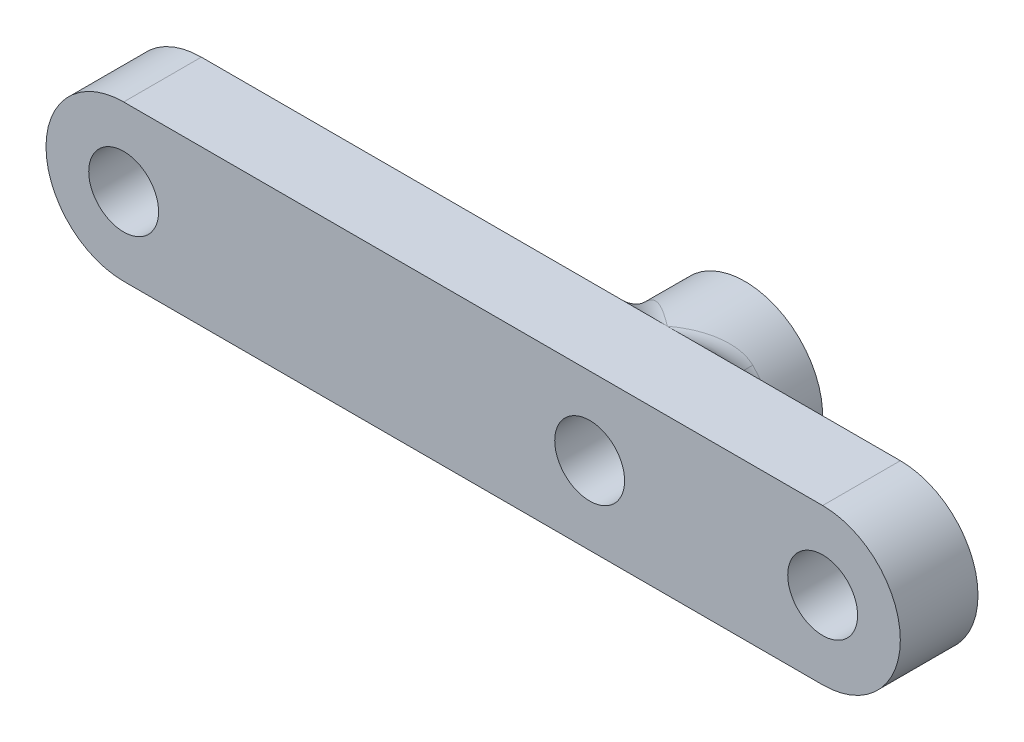
SolidWorks part; units mm, degrees
ref_plane "Front Plane" through (0, 0, 0) normal (0, 0, 1) x (1, 0, 0)
ref_plane "Top Plane" through (0, 0, 0) normal (0, 1, 0) x (1, 0, 0)
ref_plane "Right Plane" through (0, 0, 0) normal (1, 0, 0) x (0, 0, -1)
sketch "Sketch1" plane through (0, 0, 0) normal (0, 0, 1) x (1, 0, 0)
  line L0 (-30, 0) -> (15, 0) construction
  line L1 (-30, 5) -> (15, 5)
  line L2 (-30, -5) -> (15, -5)
  arc A0 (-30, 5) -> (-30, -5) centre (-30, 0) ccw
  arc A1 (15, -5) -> (15, 5) centre (15, 0) ccw
  point P3 (-7.5, 0)
  dimension "D1" = 30
  dimension "D2" = 15
  dimension "D3" = 10
extrude "Boss-Extrude1" add sketch "Sketch1" along normal mid plane 5
sketch "Sketch2" plane through (0, 0, -2.5) normal (0, 0, -1) x (-1, 0, 0)
  circle A0 centre (0, 0) radius 5
  dimension "D1" = 10
extrude "Boss-Extrude2" add sketch "Sketch2" along normal blind 5
hole_wizard "M4 Clearance Hole1" positions "Sketch3" profile "Sketch4" hole size "M4" standard "ANSI Metric" end condition through all
sketch "Sketch3" plane through (0, 0, -7.5) normal (0, 0, -1) x (-1, 0, 0)
  point P0 (0, 0)
  point P3 (30, 0)
  point P7 (-15, 0)
sketch "Sketch4" plane through (0, 0, -7.5) normal (1, 0, 0) x (0, 1, 0)
  line L0 (0, 0) -> (0, 10)
  line L1 (0, 10) -> (2.25, 10)
  line L2 (2.25, 10) -> (2.25, 0)
  line L5 (2.25, 0) -> (0, 0)
  line L11 (0, -6.35) -> (0, 107.95) construction
  dimension "Thru Hole Dia." = 4.5
  dimension "Thru Hole Depth" = 10
fillet "Fillet1" radius 2 2 edges at (5, 0, -2.5) (-5, 0, -2.5)
